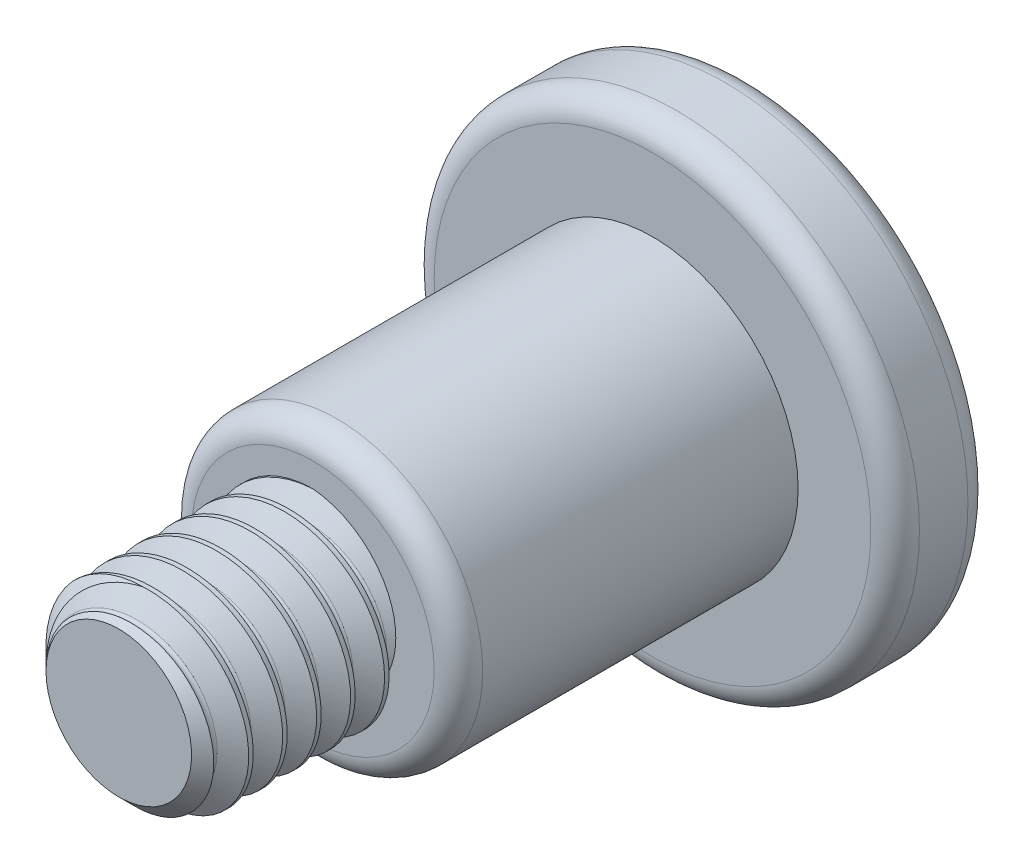
SolidWorks part; units mm, degrees
material "AR-M2"
ref_plane "正面" through (0, 0, 0) normal (0, 0, 1) x (1, 0, 0)
ref_plane "平面" through (0, 0, 0) normal (0, 1, 0) x (1, 0, 0)
ref_plane "右側面" through (0, 0, 0) normal (1, 0, 0) x (0, 0, -1)
sketch "ｽｹｯﾁ1" plane through (0, 0, 0) normal (1, 0, 0) x (0, 0, -1)
  line L0 (-4.522, 0) -> (3.5383, 0) construction
  line L1 (2, 0) -> (2, 5)
  line L2 (2, 5) -> (0, 5)
  line L3 (0, 5) -> (0, 3)
  line L4 (0, 3) -> (-7, 3)
  line L5 (-7, 3) -> (-7, 2)
  line L6 (-7, 2) -> (-11, 2)
  line L7 (-11, 2) -> (-11, 0)
  line L8 (-11, 0) -> (2, 0)
  dimension "D1" = 6
  dimension "D2" = 7
  dimension "D3" = 2
  dimension "D4" = 10
  dimension "D5" = 4
  dimension "D6" = 4
revolve "回転1" add sketch "ｽｹｯﾁ1" angle 360 about L0
fillet "ﾌｨﾚｯﾄ1" radius 0.5 3 edges at (5, 0, -2) (5, 0, 0) (3, 0, 7)
chamfer "面取り1" distance 0.5 angle 45 1 edges at (2, 0, 11)
sketch "ｽｹｯﾁ8" plane through (0, 0, 0) normal (1, 0, 0) x (0, 0, -1)
  line L0 (-11, 0) -> (-7, 0) construction
  line L1 (-11, 1.5) -> (-11, -1.5) construction
  line L2 (-7, 2) -> (-7, -2) construction
  line L3 (-10.5, 2) -> (-7, 2)
  line L4 (-7, -2) -> (-10.5, -2)
  line L5 (-7, -2) -> (-10.5, -2) construction
  line L6 (-10.5, 2) -> (-7, 2) construction
  line L7 (-7, 2.0758) -> (-10.5, 2.0758) construction
  line L8 (-7, 2.5) -> (-7, -2.5) construction
  line L9 (-7.3039, 2.0758) -> (-7.3039, 1.4736) construction
  line L10 (-7.3039, 1.4736) -> (-6.9563, 2.0758) construction
  line L11 (-6.9563, 2.0758) -> (-7.3039, 2.0758) construction
  line L12 (-7.3039, 1.4736) -> (-7.6516, 2.0758) construction
  line L13 (-7.3039, 1.4736) -> (-7, 1.4736) construction
  line L14 (-7, 1.6) -> (-10.5, 1.6) construction
  line L15 (-10.5, 2) -> (-10.5, -2) construction
  line L16 (-7.239, 1.5861) -> (-7, 2)
  line L17 (-7, 2) -> (-7.6078, 2)
  line L18 (-7.6078, 2) -> (-7.3689, 1.5861)
  arc A0 (-7.3689, 1.5861) -> (-7.239, 1.5861) centre (-7.3039, 1.6236) ccw
  dimension "D5" = 0.15
  dimension "D1" = 0.0758
  dimension "D2" = 60
  dimension "D3" = 0.6022
  dimension "D4" = 3.2
sketch "ｽｹｯﾁ9" plane through (0, 0, 7) normal (0, 0, 1) x (1, 0, 0)
  circle A0 centre (0, 0) radius 2 construction
  circle A1 centre (0, 0) radius 2
curve "ﾍﾘｶﾙ ｶｰﾌﾞ/ｽﾊﾟｲﾗﾙ ｶｰﾌﾞ1" pitch 0.7 height 5.6 radius 2 centre (0, 0, 7) axis (0, 0, 1) start towards (0, 1, 0)
sweep "ｶｯﾄ - ｽｲｰﾌﾟ1" cut profiles "ｽｹｯﾁ8" path "ﾍﾘｶﾙ ｶｰﾌﾞ/ｽﾊﾟｲﾗﾙ ｶｰﾌﾞ1" align with end faces yes
equation "\"D1@ｽｹｯﾁ8\"=0.7/8*0.866025"
equation "\"D3@ｽｹｯﾁ8\"=0.86025*0.7"
